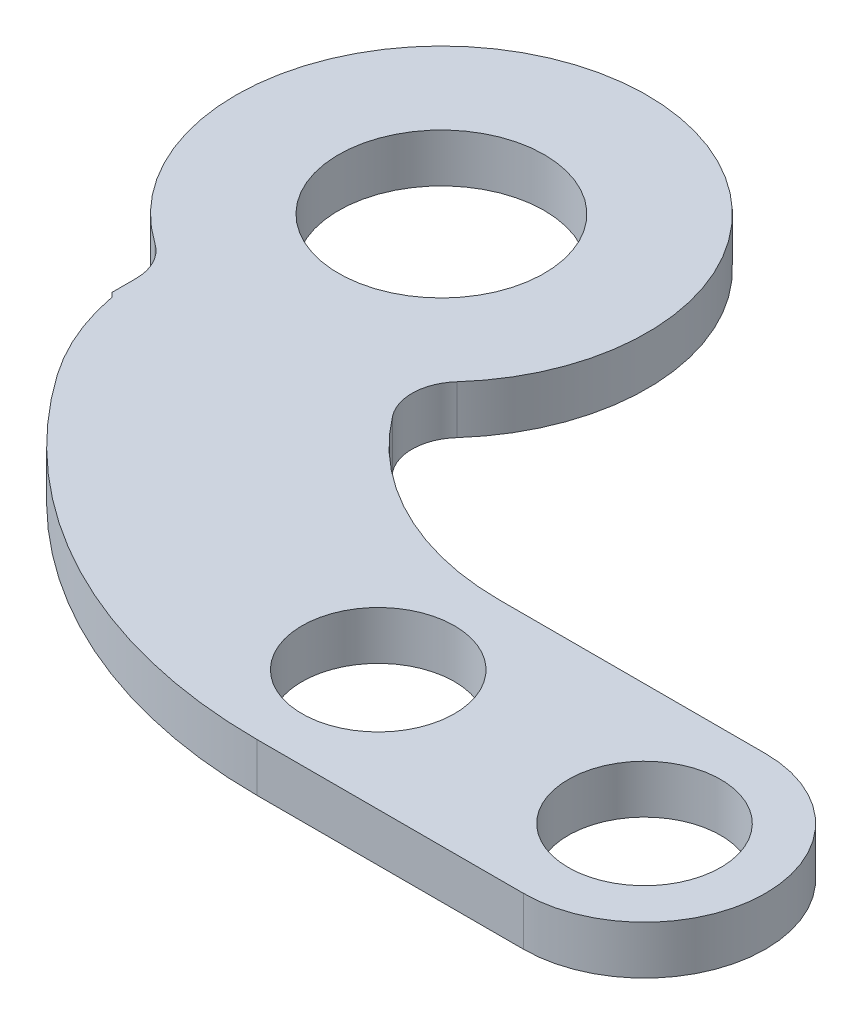
SolidWorks part; units mm, degrees
material "Copper"
ref_plane "Front Plane" through (0, 0, 0) normal (0, 0, 1) x (1, 0, 0)
ref_plane "Top Plane" through (0, 0, 0) normal (0, 1, 0) x (1, 0, 0)
ref_plane "Right Plane" through (0, 0, 0) normal (1, 0, 0) x (0, 0, -1)
sketch "Sketch1" plane through (0, 0, 0) normal (1, 0, 0) x (0, 0, -1)
  line L1 (0, 0) -> (-10.11, 0)
  point P6 (0, 0)
  dimension "D4" = 10.11
extrude "Extrude-Thin1" add sketch "Sketch1" along normal blind 8 thin thin type mid plane wall 2
chamfer "Chamfer1" distance 8 angle 45 1 edges at (0, 0, 10.11)
sketch "Sketch2" plane through (0, 1, 0) normal (0, 1, 0) x (1, 0, 0)
  line L0 (8, -10.11) -> (30, -10.11) construction
  line L1 (0, -0.4346) -> (0, 0)
  line L2 (19, -5.11) -> (30, -5.11)
  line L3 (19, -15.11) -> (30, -15.11)
  line L4 (8, 0) -> (8, -10.11) construction
  line L6 (8, 0) -> (8, -10.11) construction
  line L7 (0, 0) -> (0, -2.11) construction
  arc A0 (19, -15.11) -> (1.8182, -6.1842) centre (19, 5.89) cw
  circle A1 centre (30, -10.11) radius 3.15
  circle A2 centre (19, -10.11) radius 3.15
  arc A3 (30, -15.11) -> (30, -5.11) centre (30, -10.11) ccw
  arc A4 (1.8182, -6.1842) -> (0, -0.4346) centre (10, -0.4346) cw
  arc A5 (0, 0) -> (8.2952, 3.3589) centre (-0.4619, 13.0629) ccw
  arc A6 (19, -5.11) -> (8.2952, 3.3589) centre (19, 5.89) cw
  point P4 (19, -10.11)
  point P13 (8, -83.1034)
  dimension "D1" = 6.3
  dimension "D2" = 5
  dimension "D6" = 10
  dimension "D4" = 11
  dimension "D5" = 11
extrude "Boss-Extrude1" add sketch "Sketch2" against normal blind 2
sketch "Sketch6" plane through (0, -1, 0) normal (0, -1, 0) x (1, 0, 0)
  circle A0 centre (4, -7.5) radius 4.25
  circle A1 centre (4, -7.5) radius 8.5
  dimension "D1" = 17
  dimension "D2" = 8.5
extrude "Boss-Extrude4" add sketch "Sketch6" against normal blind 2
fillet "Fillet4" radius 2 2 edges at (0, 0, 0) (9.2433, 0, -0.8099)
